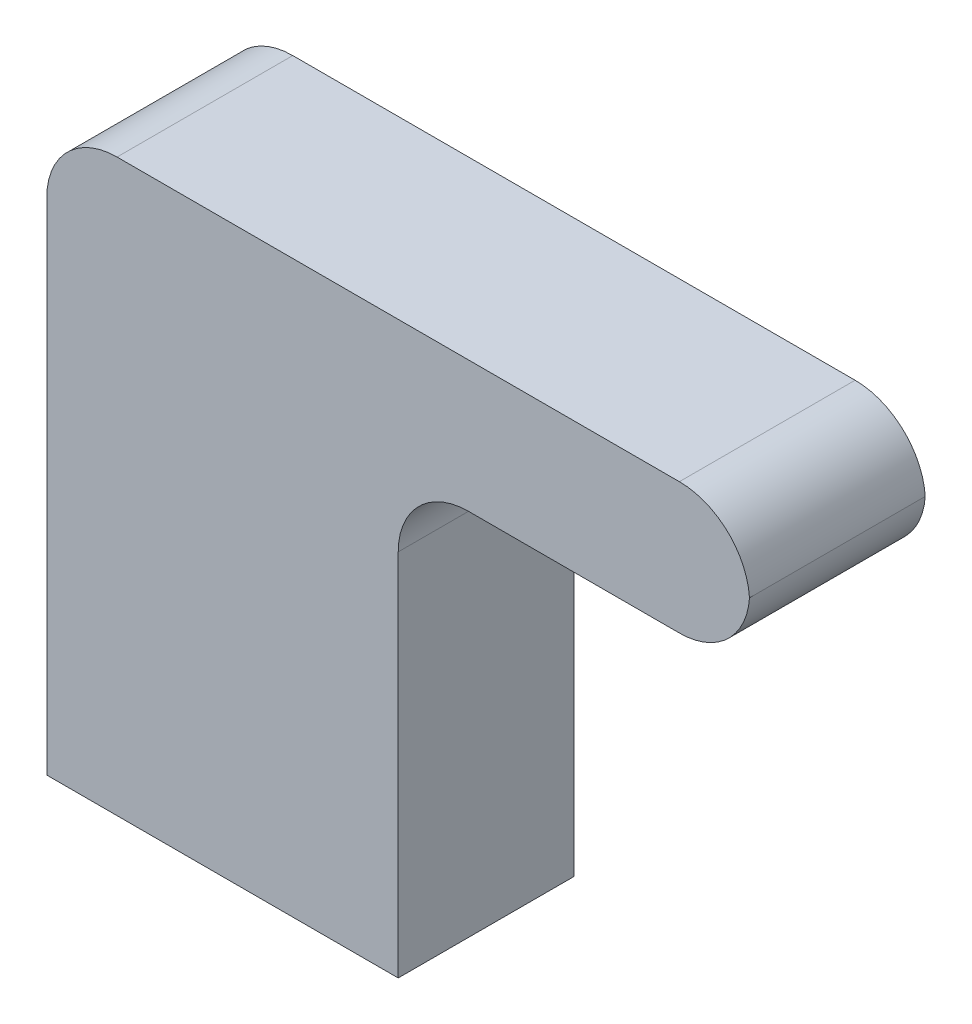
SolidWorks part; units mm, degrees
material "6061-T6 (SS)"
ref_plane "Front Plane" through (0, 0, 0) normal (0, 0, 1) x (1, 0, 0)
ref_plane "Top Plane" through (0, 0, 0) normal (0, 1, 0) x (1, 0, 0)
ref_plane "Right Plane" through (0, 0, 0) normal (1, 0, 0) x (0, 0, -1)
sketch "Sketch1" plane through (0, 0, 0) normal (0, 0, 1) x (1, 0, 0)
  line L0 (0, 0) -> (0, 15.875)
  line L1 (0, 15.875) -> (12.7, 15.875)
  line L2 (12.7, 15.875) -> (12.7, 20.6121)
  line L3 (12.7, 20.6121) -> (-12.7, 20.6121)
  line L4 (-12.7, 20.6121) -> (-12.7, 0)
  line L5 (-12.7, 0) -> (0, 0)
  dimension "D1" = 12.7
  dimension "D2" = 20.6121
  dimension "D3" = 15.875
  dimension "D4" = 25.4
extrude "Boss-Extrude1" add sketch "Sketch1" along normal blind 6.35
fillet "Fillet1" radius 2.54 4 edges at (0, 15.875, 3.175) (12.7, 15.875, 3.175) (12.7, 20.6121, 3.175) (-12.7, 20.6121, 3.175)
